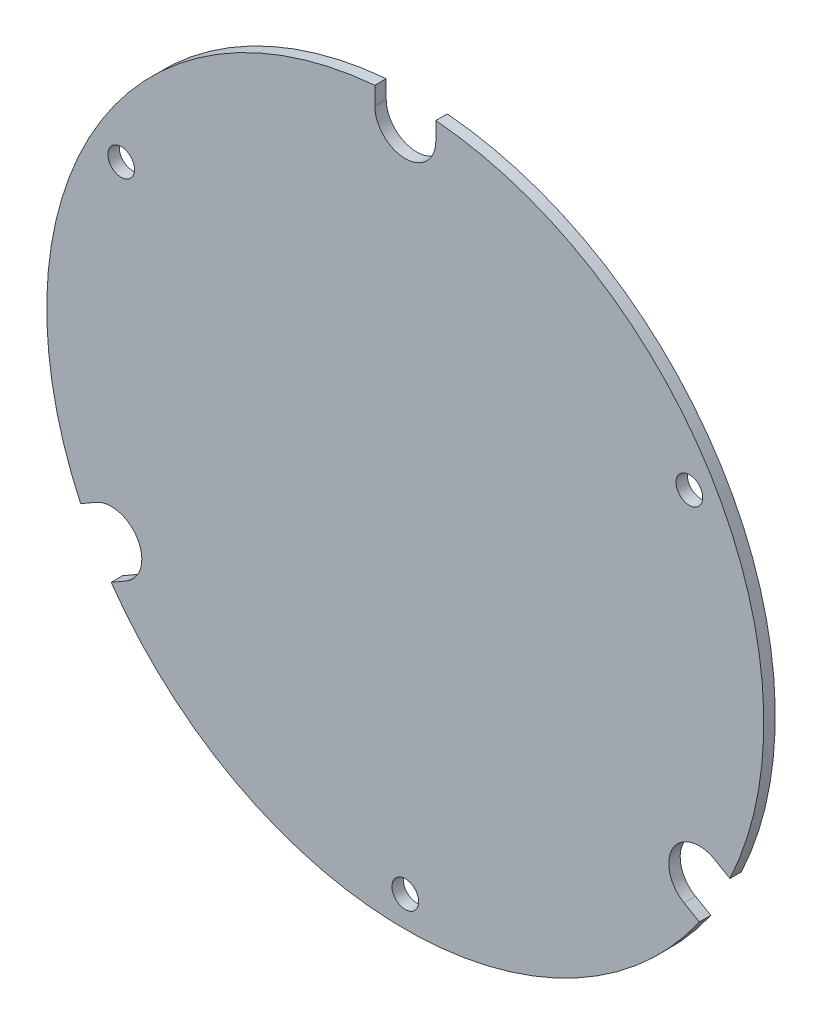
SolidWorks part; units mm, degrees
ref_plane "Alzado" through (0, 0, 0) normal (0, 0, 1) x (1, 0, 0)
ref_plane "Planta" through (0, 0, 0) normal (0, 1, 0) x (1, 0, 0)
ref_plane "Vista lateral" through (0, 0, 0) normal (1, 0, 0) x (0, 0, -1)
sketch "Croquis1" plane through (0, 0, 0) normal (0, 0, 1) x (1, 0, 0)
  line L0 (-3, 44.5) -> (-3, 47.9062) construction
  line L1 (3, 44.5) -> (3, 47.9062) construction
  line L2 (0, 44.5) -> (0, 0) construction
  line L3 (37.0381, -24.8481) -> (39.988, -26.5512) construction
  line L4 (40.0381, -19.6519) -> (42.988, -21.355) construction
  line L5 (-40.0381, -19.6519) -> (-42.988, -21.355) construction
  line L6 (-37.0381, -24.8481) -> (-39.988, -26.5512) construction
  line L7 (0, 0) -> (0, 44.5) construction
  line L8 (0, 0) -> (38.5381, -22.25) construction
  line L9 (-4, 44.5) -> (-4, 46.8295)
  line L10 (-40.5381, -18.7859) -> (-42.5555, -19.9506)
  line L11 (-36.5381, -25.7141) -> (-38.5555, -26.8788)
  line L12 (36.5381, -25.7141) -> (38.5555, -26.8788)
  line L13 (40.5381, -18.7859) -> (42.5555, -19.9506)
  line L14 (4, 44.5) -> (4, 46.8295)
  line L15 (1, 44.5) -> (1, 0)
  arc A0 (-39.988, -26.5512) -> (39.988, -26.5512) centre (0, 0) ccw construction
  arc A1 (-3, 44.5) -> (3, 44.5) centre (0, 44.5) ccw construction
  arc A2 (40.0381, -19.6519) -> (37.0381, -24.8481) centre (38.5381, -22.25) ccw construction
  arc A3 (-37.0381, -24.8481) -> (-40.0381, -19.6519) centre (-38.5381, -22.25) ccw construction
  arc A4 (42.988, -21.355) -> (3, 47.9062) centre (0, 0) ccw construction
  arc A5 (-3, 47.9062) -> (-42.988, -21.355) centre (0, 0) ccw construction
  arc A6 (-4, 46.8295) -> (-42.5555, -19.9506) centre (0, 0) ccw
  arc A7 (-36.5381, -25.7141) -> (-40.5381, -18.7859) centre (-38.5381, -22.25) ccw
  arc A8 (-38.5555, -26.8788) -> (38.5555, -26.8788) centre (0, 0) ccw
  arc A9 (40.5381, -18.7859) -> (36.5381, -25.7141) centre (38.5381, -22.25) ccw
  arc A10 (42.5555, -19.9506) -> (4, 46.8295) centre (0, 0) ccw
  arc A11 (-4, 44.5) -> (4, 44.5) centre (0, 44.5) ccw
  point P0 (38.5381, -22.25)
  point P9 (0, 0)
  dimension "D1" = 96
  dimension "D2" = 44.5
  dimension "D3" = 6
  dimension "D4" = 3
  dimension "D5" = 120
  dimension "D6" = 1
extrude "Saliente-Extruir1" add sketch "Croquis1" along normal blind 1.5 contours A11 L9 A6 L10 A7 L11 A8 L12 A9 L13 A10 L14 region at (0, 0, 0)
sketch "Croquis2" plane through (0, 0, 1.5) normal (0, 0, 1) x (1, 0, 0)
  line L0 (0, 0) -> (-37.2391, 21.5) construction
  line L1 (0, 0) -> (0, 40.5) construction
  line L2 (0, 0) -> (-37.2391, 21.5) construction
  line L3 (0, 0) -> (37.2391, 21.5) construction
  circle A0 centre (-37.2391, 21.5) radius 1.75
  arc A1 (-4, 44.5) -> (4, 44.5) centre (0, 44.5) ccw construction
  circle A2 centre (37.2391, 21.5) radius 1.75
  circle A3 centre (0, -43) radius 1.75
  point P3 (34.4744, 10.7214)
  dimension "D1" = 3.5
  dimension "D2" = 60
  dimension "D3" = 43
  dimension "D5" = 120
  dimension "D4" = 3
extrude "Cortar-Extruir1" cut sketch "Croquis2" against normal blind 1.5
